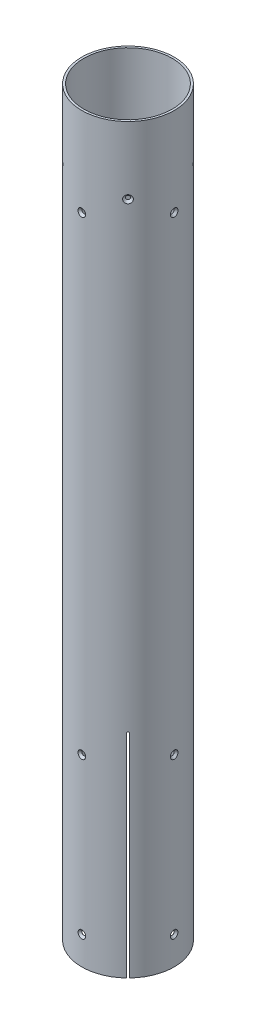
SolidWorks part; units mm, degrees
material "E-Cam Elyafı"
ref_plane "Ön Düzlem" through (0, 0, 0) normal (0, 0, 1) x (1, 0, 0)
ref_plane "Üst Düzlem" through (0, 0, 0) normal (0, 1, 0) x (1, 0, 0)
ref_plane "Sağ Düzlem" through (0, 0, 0) normal (1, 0, 0) x (0, 0, -1)
sketch "Çizim1" plane through (0, 0, 0) normal (0, 1, 0) x (1, 0, 0)
  circle A0 centre (0, 0) radius 65.5
  circle A1 centre (0, 0) radius 62.5
  dimension "D1" = 131
  dimension "D2" = 125
extrude "Yükseklik-Ekstrüzyon1" add sketch "Çizim1" along normal mid plane 1050
sketch "Çizim2" plane through (0, -525, 0) normal (0, -1, 0) x (1, 0, 0)
  line L0 (0, 0) -> (65.5, 0) construction
  line L1 (65.5, 36.6899) -> (65.5, -36.6899) construction
  circle A0 centre (0, 0) radius 65.5 construction
  point P9 (65.5, 0)
sketch "Çizim3" plane through (0, 525, 0) normal (0, 1, 0) x (1, 0, 0)
  line L0 (0, 0) -> (65.5, 0) construction
ref_plane "Düzlem1" through (65.5, 0, 0) normal (-1, 0, 0) x (0, 0, 1)
sketch "Çizim4" plane through (65.5, 0, 0) normal (-1, 0, 0) x (0, 0, 1)
  line L0 (0, -525) -> (0, 500.9426) construction
  line L1 (36.6899, -525) -> (-36.6899, -525) construction
  line L2 (-31.735, -485) -> (31.735, -485) construction
  line L3 (-31.735, -264.84) -> (31.735, -264.84) construction
  line L4 (-31.735, 399.74) -> (31.735, 399.74) construction
  point P8 (0, -485)
  point P11 (0, -264.84)
  point P14 (0, 399.74)
  dimension "D1" = 40
  dimension "D2" = 260.16
  dimension "D3" = 924.74
hole_wizard "M5 Altıgen Alyan Havşa Başlı Kör Vida İçin Havşa3" positions "Çizim4" profile "Çizim14" countersink size "M5" standard "ISO"
sketch "Çizim14" plane through (65.5, 399.74, 0) normal (0, 1, 0) x (0, 0, -1)
  line L0 (0, 0) -> (0, 16.5923)
  line L1 (0, 16.5923) -> (2.65, 15)
  line L2 (2.65, 15) -> (2.65, 2.95)
  line L3 (2.65, 2.95) -> (5.6, 0)
  line L5 (5.6, 0) -> (0, 0)
  line L6 (-2.65, 2.95) -> (-5.6, 0) construction
  line L10 (0, 16.5923) -> (-2.65, 15) construction
  line L11 (0, -6.35) -> (0, 107.95) construction
  dimension "Hole Dia." = 5.3
  dimension "Hole Depth" = 15
  dimension "Near C'Sink Dia." = 11.2
  dimension "Near C'Sink Angle" = 90
  dimension "Drill Angle" = 118
pattern_circular "Dairesel Kaplama2" count 4 over 360 about axis through (0, 525, 0) along (0, 1, 0) of "M5 Altıgen Alyan Havşa Başlı Kör Vida İçin Havşa3"
sketch "Çizim15" plane through (0, -525, 0) normal (0, -1, 0) x (1, 0, 0)
  line L0 (0, 0) -> (46.3155, 46.3155) construction
  line L1 (0, 0) -> (30.9499, 0) construction
  circle A0 centre (0, 0) radius 65.5 construction
  dimension "D1" = 45
sketch "Çizim16" plane through (0, 525, 0) normal (0, 1, 0) x (1, 0, 0)
  line L0 (0, 0) -> (46.3155, -46.3155) construction
  line L1 (30.4133, -62.2177) -> (62.2177, -30.4133) construction
  point P7 (46.3155, -46.3155)
ref_plane "Düzlem3" through (46.3155, 0, 46.3155) normal (0.7071, 0, 0.7071) x (0.7071, 0, -0.7071)
sketch "Çizim17" plane through (46.3155, 0, 46.3155) normal (0.7071, 0, 0.7071) x (0.7071, 0, -0.7071)
  line L0 (0, -525) -> (0, 429.7) construction
  line L1 (-65.5, -525) -> (65.5, -525) construction
  point P1 (0, 429.7)
  point P9 (0, 429.7)
  dimension "D1" = 954.7
hole_wizard "M5 Altıgen Alyan Havşa Başlı Kör Vida İçin Havşa4" positions "Çizim17" profile "Çizim18" countersink size "M5" standard "ISO"
sketch "Çizim18" plane through (46.3155, 429.7, 46.3155) normal (0, 1, 0) x (0.7071, 0, -0.7071)
  line L0 (0, 0) -> (0, 16.5923)
  line L1 (0, 16.5923) -> (2.65, 15)
  line L2 (2.65, 15) -> (2.65, 2.95)
  line L3 (2.65, 2.95) -> (5.6, 0)
  line L5 (5.6, 0) -> (0, 0)
  line L6 (-2.65, 2.95) -> (-5.6, 0) construction
  line L10 (0, 16.5923) -> (-2.65, 15) construction
  line L11 (0, -6.35) -> (0, 107.95) construction
  dimension "Hole Dia." = 5.3
  dimension "Hole Depth" = 15
  dimension "Near C'Sink Dia." = 11.2
  dimension "Near C'Sink Angle" = 90
  dimension "Drill Angle" = 118
pattern_circular "Dairesel Kaplama3" count 4 over 360 about axis through (0, 525, 0) along (0, 1, 0) of "M5 Altıgen Alyan Havşa Başlı Kör Vida İçin Havşa4"
sketch "Çizim20" plane through (0, -525, 0) normal (0, -1, 0) x (1, 0, 0)
  line L0 (0, 0) -> (-22.7346, 22.7346) construction
  line L1 (0, 0) -> (-30.9499, 0) construction
  line L2 (-27.8138, 17.6554) -> (-17.6554, 27.8138) construction
  point P7 (-22.7346, 22.7346)
  point P9 (-46.3155, 46.3155)
  dimension "D1" = 45
sketch "Çizim22" plane through (0, 525, 0) normal (0, 1, 0) x (1, 0, 0)
  line L0 (-22.7346, -22.7346) -> (0, 0) construction
ref_plane "Düzlem4" through (-22.7346, 0, 22.7346) normal (0.7071, 0, -0.7071) x (-0.7071, 0, -0.7071)
sketch "Çizim23" plane through (-22.7346, 0, 22.7346) normal (0.7071, 0, -0.7071) x (-0.7071, 0, -0.7071)
  line L0 (0, -525) -> (0, -225) construction
  line L1 (-65.5, -525) -> (65.5, -525) construction
  line L3 (-1.6, -225) -> (-1.6, -525)
  line L4 (1.6, -525) -> (1.6, -225)
  line L5 (-1.6, -525) -> (1.6, -525)
  arc A0 (1.6, -225) -> (-1.6, -225) centre (0, -225) ccw
  point P8 (0, -225)
  dimension "D1" = 300
  dimension "D2" = 3.2
extrude "Kes-Ekstrüzyon2" cut sketch "Çizim23" against normal blind 1050
pattern_circular "Dairesel Kaplama4" count 4 over 360 about axis through (0, -525, 0) along (0, 1, 0) of "Kes-Ekstrüzyon2"
